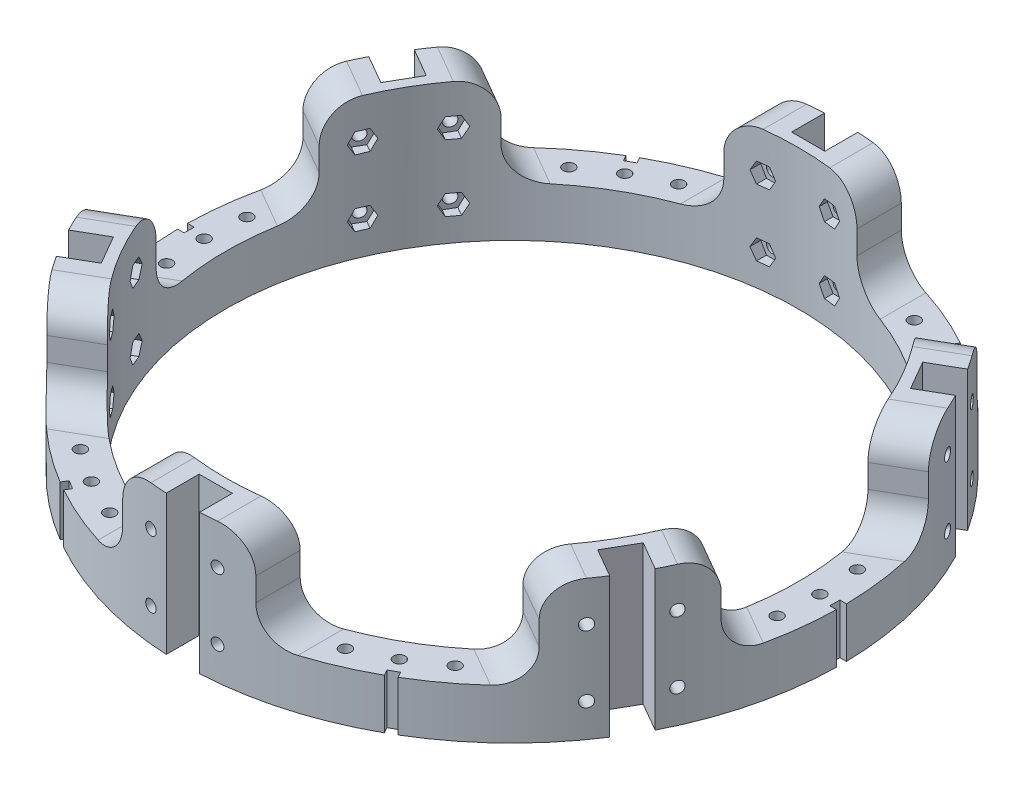
SolidWorks part; units mm, degrees
ref_plane "Спереди" through (0, 0, 0) normal (0, 0, 1) x (1, 0, 0)
ref_plane "Сверху" through (0, 0, 0) normal (0, 1, 0) x (1, 0, 0)
ref_plane "Справа" through (0, 0, 0) normal (1, 0, 0) x (0, 0, -1)
sketch "Эскиз1" plane through (0, 0, 0) normal (0, 1, 0) x (1, 0, 0)
  circle A0 centre (0, 0) radius 86
  circle A1 centre (0, 0) radius 99
  dimension "D1" = 198
  dimension "D2" = 172
extrude "Бобышка-Вытянуть1" add sketch "Эскиз1" along normal blind 15
sketch "Эскиз2" plane through (0, 15, 0) normal (0, 1, 0) x (1, 0, 0)
  line L0 (0, 0) -> (0, 94) construction
  line L1 (-5, 99) -> (5, 99)
  line L2 (-5, 99) -> (-5, 89)
  line L3 (-5, 89) -> (5, 89)
  line L4 (5, 99) -> (5, 89)
  line L5 (-5, 99) -> (5, 89) construction
  line L6 (-5, 89) -> (5, 99) construction
  circle A0 centre (0, 0) radius 99 construction
  point P0 (0, 94)
  dimension "D1" = 10
  dimension "D2" = 10
ref_plane "Плоскость1" through (0, 0, -99) normal (0, 0, -1) x (-1, 0, 0)
sketch "Эскиз5" plane through (0, 15, 0) normal (0, 1, 0) x (1, 0, 0)
  line L0 (-20, 83.6421) -> (-20, 96.9588)
  line L1 (20, 83.6421) -> (20, 96.9588)
  line L3 (0, 94) -> (-20, 94) construction
  line L4 (-5, 99) -> (5, 89) construction
  line L5 (0, 94) -> (20, 94) construction
  arc A0 (-20, 83.6421) -> (20, 83.6421) centre (0, 0) cw
  circle A1 centre (0, 0) radius 86 construction
  arc A2 (-20, 96.9588) -> (20, 96.9588) centre (0, 0) cw
  circle A3 centre (0, 0) radius 99 construction
  dimension "D1" = 40
extrude "Бобышка-Вытянуть2" add sketch "Эскиз5" along normal blind 27
extrude "Вырез-Вытянуть2" cut sketch "Эскиз2" along normal through all and the other way through all contours L3 L4 L1 L2
fillet "Скругление1" radius 10 4 edges at (-20, 15, -90.3004) (-20, 42, -90.3004) (20, 15, -90.3004) (20, 42, -90.3004)
pattern_circular "Круговой массив2" count 6 over 360 about axis through (0, 15, 0) along (0, 1, 0) of "Скругление1", "Вырез-Вытянуть2", "Бобышка-Вытянуть2"
sketch "Эскиз6" plane through (0, 15, 0) normal (0, 1, 0) x (1, 0, 0)
  line L0 (0, 0) -> (-46.25, 80.1073) construction
  line L1 (0, 0) -> (0, 94) construction
  line L2 (-46.25, 80.1073) -> (-48.5058, 84.0145) construction
  line L3 (-49.8163, 83.2847) -> (-47.1953, 84.7443)
  line L4 (-50.7894, 85.032) -> (-48.1684, 86.4916)
  line L5 (-49.8163, 83.2847) -> (-50.7894, 85.032)
  line L6 (-47.1953, 84.7443) -> (-48.1684, 86.4916)
  line L7 (0, 0) -> (-35.3982, 85.4589) construction
  line L8 (0, 0) -> (-56.3104, 73.3852) construction
  circle A0 centre (0, 0) radius 92.5 construction
  arc A2 (-30, 94.3451) -> (-66.7053, 73.1533) centre (0, 0) ccw construction
  circle A3 centre (-56.3104, 73.3852) radius 1.75
  circle A4 centre (-35.3982, 85.4589) radius 1.75
  arc A5 (-30, 80.5978) -> (-54.7997, 66.2796) centre (0, 0) ccw construction
  circle A6 centre (-46.25, 80.1073) radius 1.75
  point P14 (-48.5058, 84.0145)
  point P17 (-49.4789, 85.7618)
  dimension "D1" = 6.5
  dimension "D3" = 15
  dimension "D7" = 3.5
  dimension "D8" = 3.5
  dimension "D9" = 3.5
  dimension "D2" = 30
  dimension "D4" = 3
  dimension "D5" = 2
  dimension "D6" = 7.5
extrude "Вырез-Вытянуть3" cut sketch "Эскиз6" against normal through all
pattern_circular "Круговой массив3" count 6 over 360 about axis through (0, 15, 0) along (0, 1, 0) of "Вырез-Вытянуть3"
ref_plane "Плоскость2" through (-85.6271, 0, -49.4368) normal (0.866, 0, 0.5) x (0.5, 0, -0.866)
sketch "Эскиз7" plane through (-85.6271, 0, -49.4368) normal (0.866, 0, 0.5) x (0.5, 0, -0.866)
  line L0 (0, 0) -> (0, 10) construction
  line L1 (0, 10) -> (0, 30) construction
  line L2 (-10, 30) -> (10, 30) construction
  line L3 (10, 30) -> (10, 10) construction
  line L4 (10, 10) -> (-10, 10) construction
  line L5 (-10, 30) -> (-10, 10) construction
  circle A0 centre (10, 30) radius 1.75
  circle A1 centre (10, 10) radius 1.75
  circle A2 centre (-10, 10) radius 1.75
  circle A3 centre (-10, 30) radius 1.75
  dimension "D4" = 3.5
  dimension "D5" = 3.5
  dimension "D1" = 10
  dimension "D2" = 20
  dimension "D3" = 10
extrude "Вырез-Вытянуть4" cut sketch "Эскиз7" along normal blind 16
pattern_circular "Круговой массив4" count 6 over 360 about axis through (0, 0, 0) along (0, 1, 0) of "Вырез-Вытянуть4"
sketch "Эскиз8" plane through (0, 42, 0) normal (0, 1, 0) x (1, 0, 0)
  line L0 (-11.75, 85.1935) -> (0, 89) construction
  line L1 (-5, 89) -> (5, 89) construction
  line L2 (0, 89) -> (11.75, 85.1935) construction
  arc A0 (-8.25, 85.6034) -> (-11.75, 85.1935) centre (0, 0) ccw construction
  arc A1 (-8.25, 85.6034) -> (-11.75, 85.1935) centre (0, 0) ccw
  arc A2 (11.75, 85.1935) -> (8.25, 85.6034) centre (0, 0) ccw construction
  arc A3 (11.75, 85.1935) -> (8.25, 85.6034) centre (0, 0) ccw
ref_plane "Плоскость3" through (0, 0, -85.1935) normal (0, 0, -1) x (-1, 0, 0)
sketch "Эскиз9" plane through (0, 0, -85.1935) normal (0, 0, -1) x (-1, 0, 0)
  line L1 (8.2679, 33) -> (6.5359, 30)
  line L2 (6.5359, 30) -> (8.2679, 27)
  line L3 (8.2679, 27) -> (11.7321, 27)
  line L4 (11.7321, 27) -> (13.4641, 30)
  line L5 (13.4641, 30) -> (11.7321, 33)
  line L6 (11.7321, 33) -> (8.2679, 33)
  line L7 (-11.7321, 33) -> (-13.4641, 30)
  line L8 (-13.4641, 30) -> (-11.7321, 27)
  line L9 (-11.7321, 27) -> (-8.2679, 27)
  line L10 (-8.2679, 27) -> (-6.5359, 30)
  line L11 (-6.5359, 30) -> (-8.2679, 33)
  line L12 (-8.2679, 33) -> (-11.7321, 33)
  line L13 (-11.7321, 13) -> (-13.4641, 10)
  line L14 (-13.4641, 10) -> (-11.7321, 7)
  line L15 (-11.7321, 7) -> (-8.2679, 7)
  line L16 (-8.2679, 7) -> (-6.5359, 10)
  line L17 (-6.5359, 10) -> (-8.2679, 13)
  line L18 (-8.2679, 13) -> (-11.7321, 13)
  line L19 (8.2679, 13) -> (6.5359, 10)
  line L20 (6.5359, 10) -> (8.2679, 7)
  line L21 (8.2679, 7) -> (11.7321, 7)
  line L22 (11.7321, 7) -> (13.4641, 10)
  line L23 (13.4641, 10) -> (11.7321, 13)
  line L24 (11.7321, 13) -> (8.2679, 13)
  circle A0 centre (10, 30) radius 3 construction
  circle A1 centre (-10, 30) radius 3 construction
  circle A2 centre (-10, 10) radius 3 construction
  circle A3 centre (10, 10) radius 3 construction
  dimension "D1" = 6
  dimension "D2" = 6
  dimension "D3" = 6
  dimension "D4" = 6
extrude "Вырез-Вытянуть5" cut sketch "Эскиз9" along normal blind 3 and the other way up to next
pattern_circular "Круговой массив5" count 6 over 360 about axis through (0, 15, 0) along (0, 1, 0) of "Вырез-Вытянуть5"
